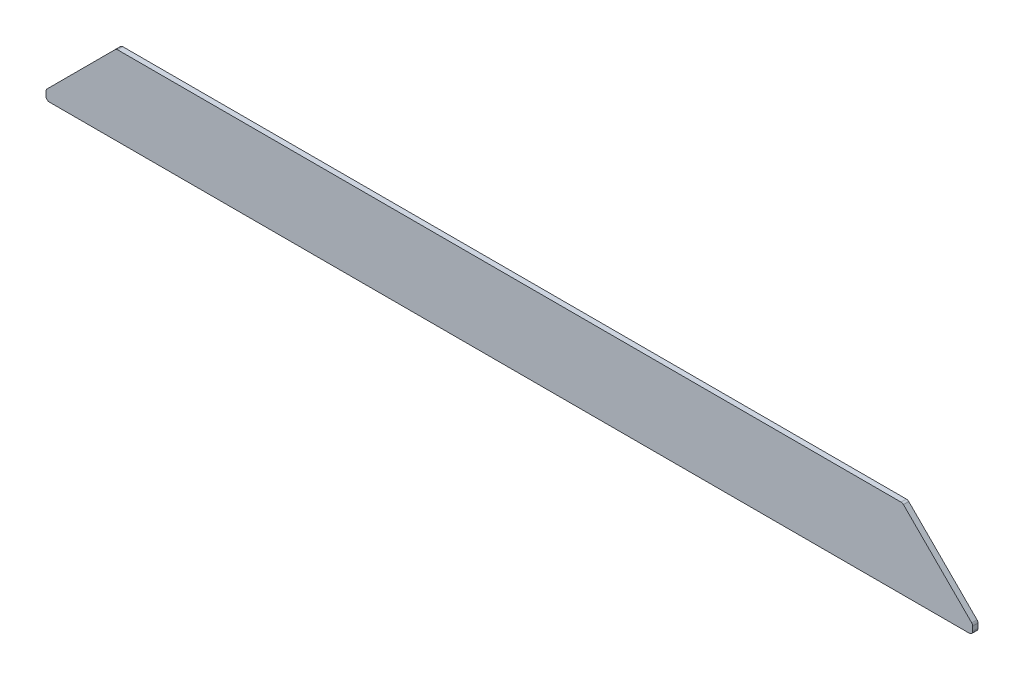
SolidWorks part; units mm, degrees
ref_plane "Front Plane" through (0, 0, 0) normal (0, 0, 1) x (1, 0, 0)
ref_plane "Top Plane" through (0, 0, 0) normal (0, 1, 0) x (1, 0, 0)
ref_plane "Right Plane" through (0, 0, 0) normal (1, 0, 0) x (0, 0, -1)
sketch "Sketch1" plane through (0, 0, 0) normal (0, 0, 1) x (1, 0, 0)
  line L0 (0, 2.7868) -> (21.2132, 24)
  line L1 (0, 0) -> (280, 0)
  line L2 (0, 0) -> (0, 24)
  line L3 (0, 24) -> (280, 24)
  line L4 (280, 0) -> (280, 24)
  line L5 (42, 0) -> (238, 0)
  line L6 (42, 0) -> (42, 11)
  line L7 (46, 15) -> (234, 15)
  line L8 (238, 0) -> (238, 11)
  line L9 (280, 2.7868) -> (258.7868, 24)
  arc A0 (234, 15) -> (238, 11) centre (234, 11) cw
  arc A1 (42, 11) -> (46, 15) centre (46, 11) cw
  dimension "D3" = 4
  dimension "D1" = 45
  dimension "D2" = 45
  dimension "D4" = 42
  dimension "D5" = 15
  dimension "D6" = 280
  dimension "D7" = 30
  dimension "D8" = 30
  dimension "D9" = 24
  dimension "D10" = 42
extrude "Boss-Extrude1" add sketch "Sketch1" along normal blind 1.6 contours L6 A1 L7 A0 L8 L1 L4 L9 L3 L0 L2 region at (140, 15.3044, 0)
fillet "Fillet1" radius 1 6 edges at (258.7868, 24, 0.8) (280, 0, 0.8) (280, 2.7868, 0.8) (0, 2.7868, 0.8) (0, 0, 0.8) (21.2132, 24, 0.8)
sketch "Sketch2" plane through (0, 0, 0) normal (0, 0, 1) x (1, 0, 0)
  line L0 (46, 15) -> (234, 15) construction
  line L5 (46, 6.8) -> (58.4, 6.8)
  line L6 (46, 6.8) -> (46, 12.55)
  line L7 (46, 12.55) -> (58.4, 12.55)
  line L8 (58.4, 6.8) -> (58.4, 12.55)
  line L45 (88.01, 6.8) -> (91.99, 6.8)
  line L46 (68.01, 6.8) -> (71.99, 6.8)
  line L47 (221.6, 6.8) -> (234, 6.8)
  line L48 (221.6, 6.8) -> (221.6, 12.55)
  line L49 (221.6, 12.55) -> (234, 12.55)
  line L50 (234, 6.8) -> (234, 12.55)
  line L51 (42, 0) -> (42, 11) construction
  line L52 (238, 0) -> (238, 11) construction
  line L53 (68.01, 6.8) -> (68.01, 8.5)
  line L54 (68.01, 8.5) -> (71.99, 8.5)
  line L55 (71.99, 6.8) -> (71.99, 8.5)
  line L56 (88.01, 6.8) -> (88.01, 8.5)
  line L57 (88.01, 8.5) -> (91.99, 8.5)
  line L58 (91.99, 6.8) -> (91.99, 8.5)
  line L59 (108.01, 6.8) -> (111.99, 6.8)
  line L60 (108.01, 6.8) -> (108.01, 8.5)
  line L61 (108.01, 8.5) -> (111.99, 8.5)
  line L62 (111.99, 6.8) -> (111.99, 8.5)
  line L63 (128.01, 6.8) -> (131.99, 6.8)
  line L64 (128.01, 6.8) -> (128.01, 8.5)
  line L65 (128.01, 8.5) -> (131.99, 8.5)
  line L66 (131.99, 6.8) -> (131.99, 8.5)
  line L67 (148.01, 6.8) -> (151.99, 6.8)
  line L68 (148.01, 6.8) -> (148.01, 8.5)
  line L69 (148.01, 8.5) -> (151.99, 8.5)
  line L70 (151.99, 6.8) -> (151.99, 8.5)
  line L71 (168.01, 6.8) -> (171.99, 6.8)
  line L72 (168.01, 6.8) -> (168.01, 8.5)
  line L73 (168.01, 8.5) -> (171.99, 8.5)
  line L74 (171.99, 6.8) -> (171.99, 8.5)
  line L75 (188.01, 6.8) -> (191.99, 6.8)
  line L76 (188.01, 6.8) -> (188.01, 8.5)
  line L77 (188.01, 8.5) -> (191.99, 8.5)
  line L78 (191.99, 6.8) -> (191.99, 8.5)
  line L79 (208.01, 6.8) -> (211.99, 6.8)
  line L80 (208.01, 6.8) -> (208.01, 8.5)
  line L81 (208.01, 8.5) -> (211.99, 8.5)
  line L82 (211.99, 6.8) -> (211.99, 8.5)
  line L83 (68.01, 6.8) -> (88.01, 6.8) construction
  line L84 (131.99, 6.8) -> (148.01, 6.8)
  line L85 (0, 0) -> (280, 0) construction
  point P10 (140, 6.8)
  point P49 (140, 15)
  dimension "D2" = 8
  dimension "D3" = 12.4
  dimension "D4" = 5.75
  dimension "D5" = 20
  dimension "D7" = 1.7
  dimension "D8" = 12.4
  dimension "D9" = 5.75
  dimension "D10" = 4
  dimension "D11" = 4
  dimension "D6" = 6.8
  dimension "D12" = 3.98
  dimension "D13" = 6.5
extrude "Boss-Extrude2" add sketch "Sketch1<3>" along normal blind 1.6 contours A1 L6 L1 L8 A0 L7 region at (140, 7.4845, 0)
sketch "Sketch1<3>" plane through (0, 0, 0) normal (0, 0, 1) x (1, 0, 0) same geometry as "Sketch1"
